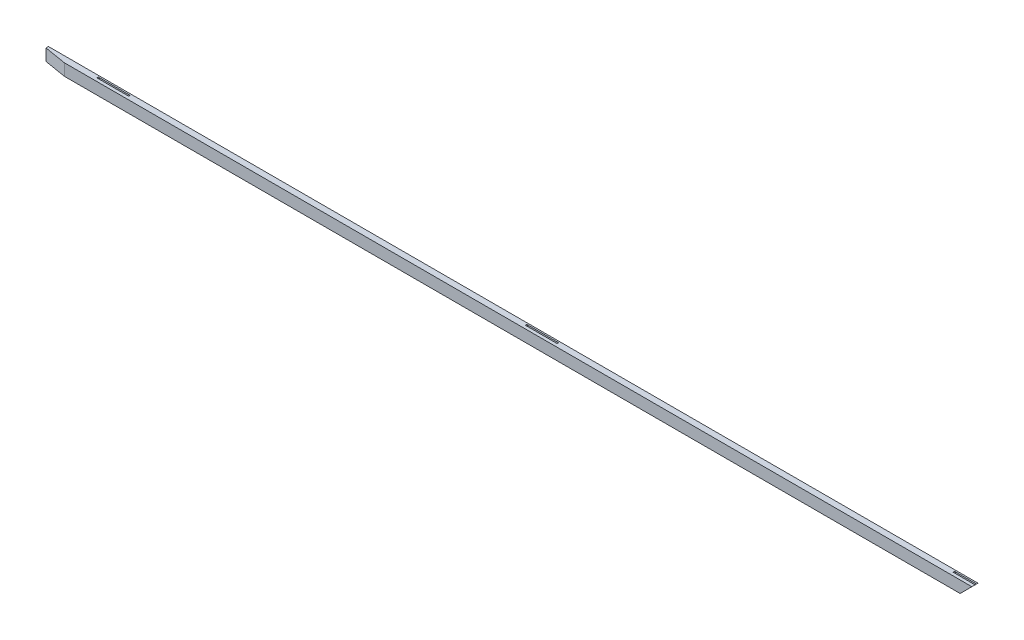
SolidWorks part; units mm, degrees
ref_plane "前视基准面" through (0, 0, 0) normal (0, 0, 1) x (1, 0, 0)
ref_plane "上视基准面" through (0, 0, 0) normal (0, 1, 0) x (1, 0, 0)
ref_plane "右视基准面" through (0, 0, 0) normal (1, 0, 0) x (0, 0, -1)
sketch "草图1" plane through (0, 0, 0) normal (0, 0, 1) x (1, 0, 0)
  line L0 (0, 24) -> (0, -24)
  line L1 (0, -24) -> (3750, -24)
  line L2 (3750, -24) -> (3798, 24)
  line L3 (3798, 24) -> (0, 24)
  point P4 (0, 0)
  dimension "D1" = 3798
  dimension "D2" = 48
  dimension "D3" = 45
extrude "凸台-拉伸1" add sketch "草图1" along normal blind 25
sketch "草图2" plane through (0, -24, 0) normal (0, -1, 0) x (1, 0, 0)
  line L0 (1967.5, 12) -> (1967.5, 6)
  line L1 (1967.5, 6) -> (2082.5, 6)
  line L2 (2082.5, 6) -> (2082.5, 12)
  line L3 (2082.5, 12) -> (1967.5, 12)
  line L4 (0, 0) -> (3750, 0) construction
  line L5 (3750, 25) -> (3798, 25) construction
  point P6 (2025, 12)
  point P9 (3774, 25)
  dimension "D1" = 115
  dimension "D2" = 6
  dimension "D3" = 6
  dimension "D4" = 1749
extrude "切除-拉伸1" cut sketch "草图2" against normal blind 7.5
draft "拔模1" type of draft neutral plane draft angle 45 faces to draft 2 face at (2082.5, -20.25, 9) face at (1967.5, -20.25, 9) neutral plane through (0, -16.5, 0) neutral plane normal (0, -1, 0) parameters "D1"=45
mirror "镜向1" about plane through (0, 0, 0) normal (0, 1, 0) of face at (1963.75, -20.25, 9) of face at (2025, -20.25, 6) of face at (2025, -16.5, 9) of face at (2025, -20.25, 12) of face at (2086.25, -20.25, 9)
pattern_linear "阵列(线性)1" count 2 spacing 1750 along (-1, 0, 0) of face at (2025, -20.25, 12) of face at (2025, -16.5, 9) of face at (1963.75, -20.25, 9) of face at (2025, -20.25, 6) of face at (2086.25, -20.25, 9) of face at (2025, 20.25, 12) of face at (1963.75, 20.25, 9) of face at (2025, 20.25, 6) of face at (2025, 16.5, 9) of face at (2086.25, 20.25, 9)
sketch "草图4" plane through (0, 0, 25) normal (0, 0, 1) x (1, 0, 0)
  line L0 (3708.5, 24) -> (3716, 16.5)
  line L1 (3798, 24) -> (0, 24) construction
  line L2 (3716, 16.5) -> (3790.5, 16.5)
  line L3 (3750, -24) -> (3798, 24) construction
  line L4 (3790.5, 16.5) -> (3798, 24)
  line L5 (3798, 24) -> (3708.5, 24)
  line L6 (3708.5, -24) -> (3716, -16.5)
  line L7 (0, -24) -> (3750, -24) construction
  line L8 (3716, -16.5) -> (3757.5, -16.5)
  line L9 (3757.5, -16.5) -> (3750, -24)
  line L10 (3750, -24) -> (3708.5, -24)
  dimension "D1" = 82
  dimension "D2" = 7.5
  dimension "D3" = 45
  dimension "D4" = 7.5
  dimension "D5" = 45
  dimension "D6" = 34
extrude "切除-拉伸3" cut sketch "草图4" against normal blind 6 from offset 13 offset against normal yes
sketch "草图5" plane through (0, -24, 0) normal (0, -1, 0) x (1, 0, 0)
  line L0 (0, 10) -> (90, 25)
  line L1 (0, 25) -> (0, 0) construction
  line L2 (0, 25) -> (3750, 25) construction
  line L3 (90, 25) -> (0, 25)
  line L4 (0, 25) -> (0, 10)
  dimension "D1" = 90
  dimension "D2" = 10
extrude "切除-拉伸4" cut sketch "草图5" against normal up to next
